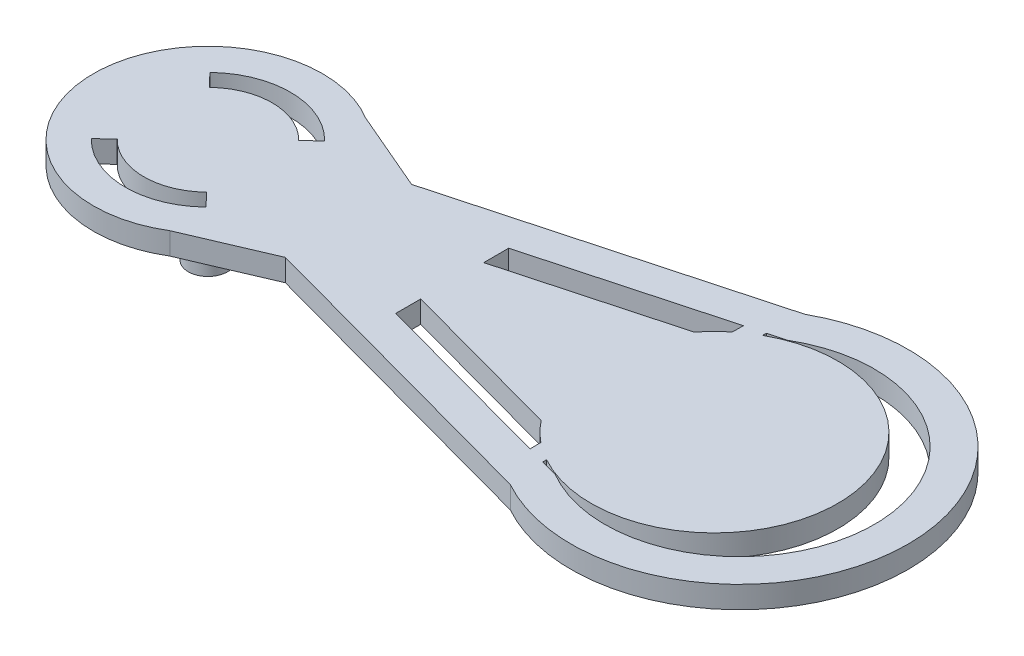
SolidWorks part; units mm, degrees
note: The reader was unsure of these and kept them because the rebuilt part matched: shared geometry of "Sketch1<4>".
ref_plane "Front Plane" through (0, 0, 0) normal (0, 0, 1) x (1, 0, 0)
ref_plane "Top Plane" through (0, 0, 0) normal (0, 1, 0) x (1, 0, 0)
ref_plane "Right Plane" through (0, 0, 0) normal (1, 0, 0) x (0, 0, -1)
sketch "Sketch1" plane through (0, 0, 0) normal (0, 1, 0) x (1, 0, 0)
  line L0 (0, 0) -> (-126.4909, 0)
  line L1 (-48.3712, -10.6702) -> (-39.5562, -6.8912)
  line L2 (-28.2349, 9.9744) -> (-28.2349, -9.9747)
  line L3 (3.1176, 14.7) -> (-28.2349, 6.1616)
  line L4 (-48.3712, 10.6702) -> (-39.5562, 6.8912)
  line L5 (-42.7478, -3) -> (-32.2365, -3)
  line L10 (3.1176, -14.7) -> (-28.2349, -6.1607)
  line L11 (-8.1046, 15.4566) -> (-8.1046, 11.6438)
  line L12 (-12.7488, -3) -> (-11.9505, -3)
  line L13 (-12.7488, 3) -> (-11.9505, 3)
  line L14 (-42.7478, 3) -> (-32.2365, 3)
  line L19 (-39.5562, 6.8912) -> (-5.8275, 16.0767)
  line L20 (-39.5562, -6.8912) -> (-5.8239, -16.0787)
  line L21 (-6.1458, 15.99) -> (-6.1458, 12.1773)
  line L22 (-8.1046, 15.4566) -> (-8.1046, 11.6438)
  line L23 (-28.2349, 3.4348) -> (-10.1848, 8.3504)
  line L24 (-6.1803, -12.1676) -> (-6.0368, -16.0207)
  line L25 (-8.1046, -11.6435) -> (-8.1046, -15.4575)
  line L26 (-28.2349, -3.4349) -> (-10.1839, -8.3513)
  line L27 (-8.1046, 11.6438) -> (-8.1195, 10.4444)
  line L28 (-6.1458, 12.1773) -> (-6.1458, 11.7781)
  line L29 (-8.1046, -11.6847) -> (-8.1228, -10.4415)
  line L30 (-6.1803, -12.1676) -> (-6.1803, -11.7587)
  line L31 (-8.1228, -10.4415) -> (-6.1803, -11.7587)
  line L32 (-6.1526, 11.7743) -> (-8.1243, 10.4404)
  arc A0 (12.0105, -16.2224) -> (12.0105, 16.2224) centre (3.1176, 0) ccw
  circle A1 centre (-54.8824, 0) radius 12.5
  circle A2 centre (-54.8824, 0) radius 2.15
  arc A3 (-32.2365, -3) -> (-25.5283, -3) centre (-28.8824, 0) ccw
  arc A4 (-25.5283, 3) -> (-32.2365, 3) centre (-28.8824, 0) ccw
  circle A7 centre (3.1176, 0) radius 14.7
  arc A8 (-5.8239, -16.0787) -> (-5.8275, 16.0767) centre (3.1176, 0) ccw
  circle A9 centre (0.3755, 0.0001) radius 13.4628
  point P8 (-1.1166, 0)
  dimension "D1" = 58
  dimension "D2" = 37
  dimension "D3" = 25
  dimension "D4" = 4.3
  dimension "D6" = 9
  dimension "D7" = 3.8
  dimension "D5" = 26
  dimension "D8" = 3
  dimension "D9" = 3
  dimension "D10" = 34.9571
  dimension "D11" = 3.6788
  dimension "D12" = 3.68
  dimension "D13" = 2.6311
  dimension "D14" = 2.63
extrude "Boss-Extrude1" add sketch "Sketch1" along normal blind 2.4
extrude "Boss-Extrude2" add sketch "Sketch1<4>" against normal blind 9 separate body contours L0 A2 | L0 A2
sketch "Sketch1<4>" plane through (0, 0, 0) normal (0, 1, 0) x (1, 0, 0) same geometry as "Sketch1"
sketch "Sketch2" plane through (0, 2.4, 0) normal (0, 1, 0) x (1, 0, 0)
  circle A0 centre (-54.8824, 0) radius 2.15
extrude "Boss-Extrude3" add sketch "Sketch2" against normal blind 9
sketch "Sketch3" plane through (0, 2.4, 0) normal (0, 1, 0) x (1, 0, 0)
  line L0 (-61.1422, 6.4665) -> (-48.6226, -6.4665)
  line L1 (-48.4159, 6.2598) -> (-61.3489, -6.2598)
  circle A0 centre (-54.8824, 0) radius 12.5
  circle A1 centre (-54.8824, 0) radius 9
  circle A2 centre (-54.8824, 0) radius 7
  dimension "D1" = 3.5
  dimension "D2" = 2
extrude "Cut-Extrude1" cut sketch "Sketch3" against normal blind 10 contours A2 L1 A1 L0 | A2 L1 A1 L0
